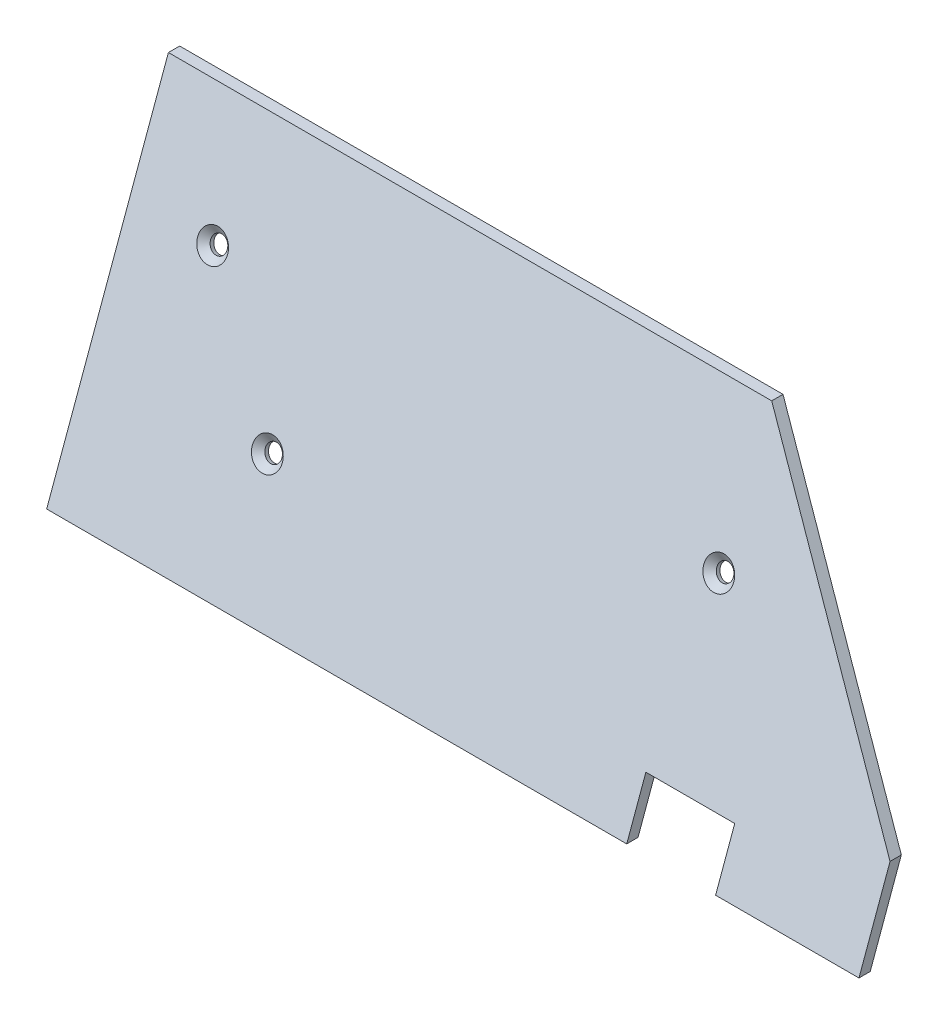
SolidWorks part; units mm, degrees
ref_plane "Front Plane" through (0, 0, 0) normal (0, 0, 1) x (1, 0, 0)
ref_plane "Top Plane" through (0, 0, 0) normal (0, 1, 0) x (1, 0, 0)
ref_plane "Right Plane" through (0, 0, 0) normal (1, 0, 0) x (0, 0, -1)
sketch "Sketch1" plane through (0, 0, 0) normal (1, 0, 0) x (0, 0, -1)
  line L0 (0, 0) -> (-2.3622, 0)
  line L1 (-2.3622, 0) -> (23.1157, 70)
  line L2 (23.1157, 70) -> (25.4779, 70)
  line L3 (25.4779, 70) -> (0, 0)
  dimension "D1" = 2.3622
  dimension "D2" = 2.3622
  dimension "D3" = 70
  dimension "D4" = 70
extrude "Main" add sketch "Sketch1" along normal mid plane 170
hole_wizard "BackBracketHoles" positions "Sketch2" profile "Sketch3" countersink size "M3" standard "ANSI Metric"
sketch "Sketch2" plane through (0, 0.7592, 2.0859) normal (0, 0.342, 0.9397) x (1, 0, 0)
  line L0 (-85, 73.6845) -> (-85, -0.8079) construction
  line L1 (85, -0.8079) -> (-85, -0.8079) construction
  point P0 (-67.6378, 50.0021)
  point P2 (-47.6378, 25.0021)
  dimension "D1" = 17.3622
  dimension "D2" = 50.81
  dimension "D3" = 25.81
  dimension "D4" = 37.3622
sketch "Sketch3" plane through (-67.6378, 47.7458, -15.0158) normal (1, 0, 0) x (0, -0.9397, 0.342)
  line L0 (0, 0) -> (0, 5)
  line L1 (0, 5) -> (1.75, 5)
  line L2 (1.75, 5) -> (1.75, 1.4)
  line L3 (1.75, 1.4) -> (3.15, 0)
  line L5 (3.15, 0) -> (0, 0)
  line L6 (-1.75, 1.4) -> (-3.15, 0) construction
  line L10 (0, 5) -> (-1.75, 5) construction
  line L11 (0, -6.35) -> (0, 107.95) construction
  dimension "Hole Dia." = 3.5
  dimension "Hole Depth" = 5
  dimension "Near C'Sink Dia." = 6.3
  dimension "Near C'Sink Angle" = 90
  dimension "Drill Angle" = 180
sketch "Sketch4" plane through (0, 0, 0) normal (0, 0, 1) x (1, 0, 0)
  line L0 (85, 0) -> (100, 0)
  line L1 (100, 0) -> (41.263, 70)
  line L2 (85, 70) -> (-85, 70) construction
  line L3 (41.263, 70) -> (41.263, 0)
  line L4 (85, 0) -> (-85, 0) construction
  line L5 (41.263, 0) -> (85, 0)
  line L6 (100, 0) -> (100, 70)
  line L7 (100, 70) -> (41.263, 70)
  line L8 (85, 70) -> (85, 0) construction
  point P12 (85, 0)
  dimension "D1" = 50
  dimension "D2" = 15
extrude "Cut-Extrude1" cut sketch "Sketch4" against normal blind 28.6 contours L6 L7 L1 region at (80.421, 46.6667, 0)
hole_wizard "CSK for M3 Flat Head Machine Screw1" positions "Sketch5" profile "Sketch6" countersink size "M3" standard "ANSI Metric"
sketch "Sketch5" plane through (0, 0.7592, 2.0859) normal (0, 0.342, 0.9397) x (1, 0, 0)
  point P0 (40, 45.0021)
  point P9 (40, 45.0021)
sketch "Sketch6" plane through (40, 43.0473, -13.3057) normal (1, 0, 0) x (0, -0.9397, 0.342)
  line L0 (0, 0) -> (0, 5)
  line L1 (0, 5) -> (1.75, 5)
  line L2 (1.75, 5) -> (1.75, 1.4)
  line L3 (1.75, 1.4) -> (3.15, 0)
  line L5 (3.15, 0) -> (0, 0)
  line L6 (-1.75, 1.4) -> (-3.15, 0) construction
  line L10 (0, 5) -> (-1.75, 5) construction
  line L11 (0, -6.35) -> (0, 107.95) construction
  dimension "Hole Dia." = 3.5
  dimension "Hole Depth" = 5
  dimension "Near C'Sink Dia." = 6.3
  dimension "Near C'Sink Angle" = 90
  dimension "Drill Angle" = 180
sketch "Sketch7" plane through (0, 0, 0) normal (0, 0, 1) x (1, 0, 0)
  line L0 (36.4, 11.002) -> (36.4, 0.002) construction
  line L1 (36.4, 11.002) -> (55, 11.002)
  line L2 (36.4, 11.002) -> (36.4, 0.002)
  line L3 (36.4, 0.002) -> (55, 0.002)
  line L4 (55, 11.002) -> (55, 0.002)
  line L6 (36.4, 11.002) -> (55, 11.002) construction
  line L7 (36.4, 0.002) -> (55, 0.002)
  line L8 (36.4, 0.002) -> (36.4, -0.998)
  line L9 (36.4, -0.998) -> (55, -0.998)
  line L10 (55, 0.002) -> (55, -0.998)
  dimension "D1" = 1
extrude "Cut-Extrude3" cut sketch "Sketch7" against normal up to surface (29.6367 mm away) from offset 30 contours L10 L3 L8 L9 | L4 L1 L2 L3 region at (45.7, 5.502, 0) region at (45.7, -0.498, 0) up to face at (40, 40.6437, -14.7931)
